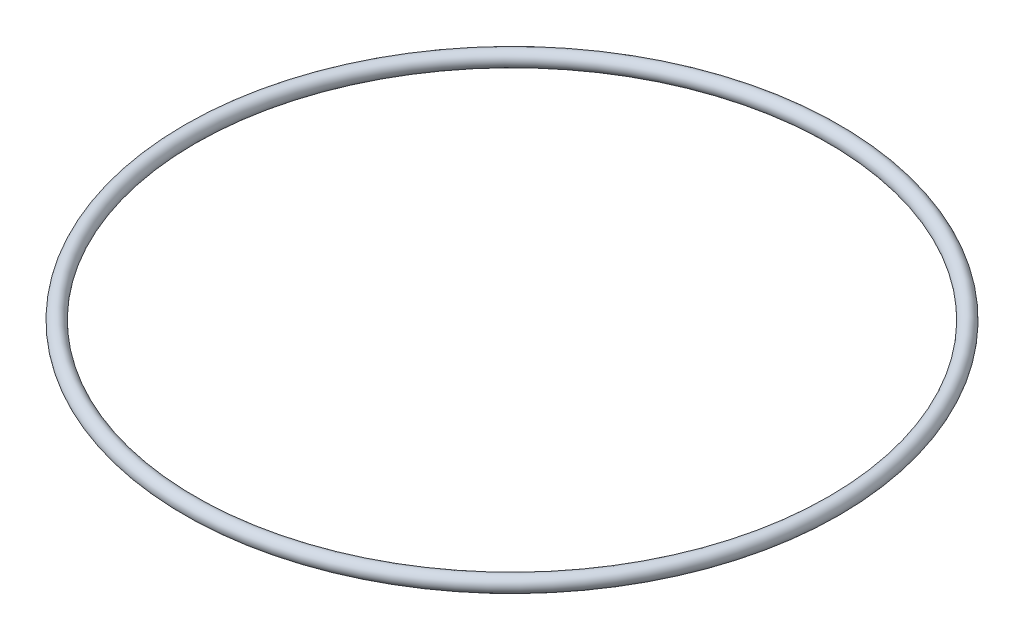
SolidWorks part; units mm, degrees
material "Silicon Rubber"
ref_plane "Front Plane" through (0, 0, 0) normal (0, 0, 1) x (1, 0, 0)
ref_plane "Top Plane" through (0, 0, 0) normal (0, 1, 0) x (1, 0, 0)
ref_plane "Right Plane" through (0, 0, 0) normal (1, 0, 0) x (0, 0, -1)
sketch "Sketch2" plane through (0, 0, 0) normal (0, 0, 1) x (1, 0, 0)
  line L0 (0, 55.4437) -> (0, -55.4437) construction
  circle A0 centre (-55.7149, 0) radius 1.3081
  point P5 (0, 0)
  dimension "D1" = 55.7149
  dimension "D2" = 2.6162
revolve "Revolve1" add sketch "Sketch2" angle 360 about L0
ref_axis "Axis1" through (0, -3.8418, 0) along (0, 1, 0)
